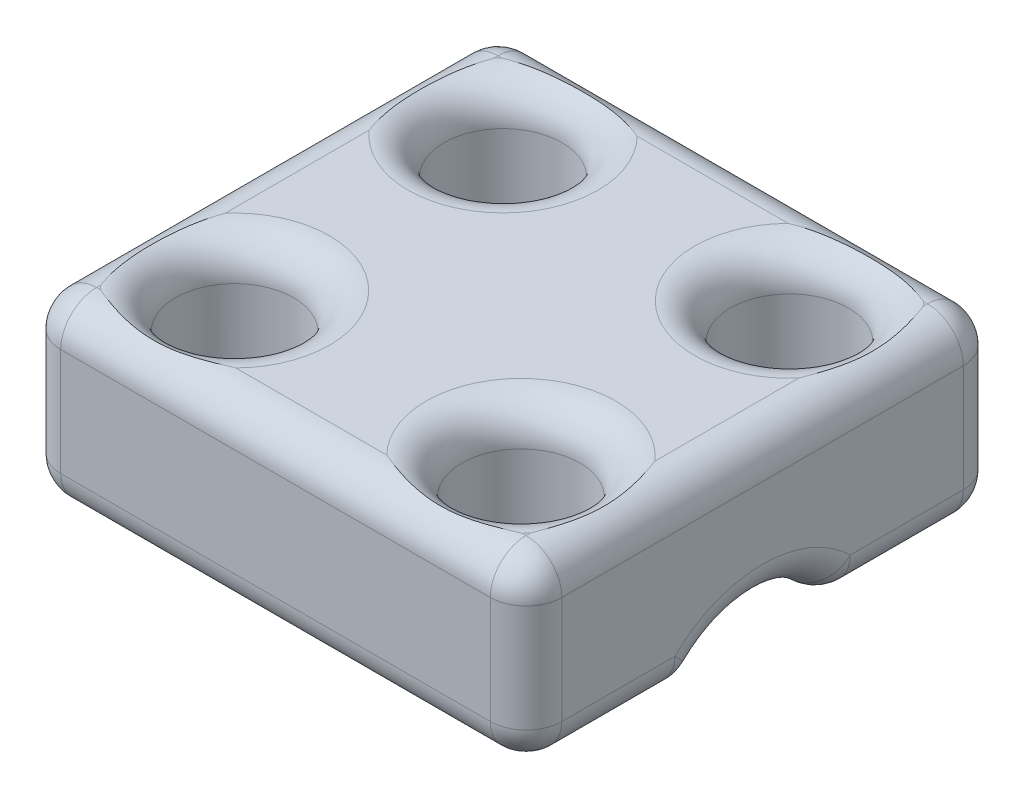
SolidWorks part; units mm, degrees
ref_plane "Front Plane" through (0, 0, 0) normal (0, 0, 1) x (1, 0, 0)
ref_plane "Top Plane" through (0, 0, 0) normal (0, 1, 0) x (1, 0, 0)
ref_plane "Right Plane" through (0, 0, 0) normal (1, 0, 0) x (0, 0, -1)
ref_axis "Axis1" through (0, 5.25, 0) along (0, -1, 0)
sketch "Sketch1" plane through (0, 0, 0) normal (0, 1, 0) x (1, 0, 0)
  line L0 (-47, 6.6067) -> (-11.7936, 6.6067) construction
  line L1 (-49, -6.6067) -> (-35, -6.6067)
  line L2 (-49, -6.6067) -> (-49, 6.6067)
  line L3 (-49, 6.6067) -> (-35, 6.6067)
  line L4 (-35, -6.6067) -> (-35, 6.6067)
  line L5 (-49, -6.6067) -> (-35, 6.6067) construction
  line L6 (-49, 6.6067) -> (-35, -6.6067) construction
  line L7 (-11.7936, -6.6067) -> (-47, -6.6067) construction
  line L8 (-49, 2.5) -> (-49, -2.5) construction
  circle A0 centre (-46, -3.75) radius 1.4 construction
  circle A1 centre (-38, -3.75) radius 1.4 construction
  circle A2 centre (-38, 3.75) radius 1.4 construction
  circle A3 centre (-46, 3.75) radius 1.4 construction
  circle A4 centre (-46, -3.75) radius 1.4 construction
  circle A5 centre (-38, -3.75) radius 1.4 construction
  circle A6 centre (-38, 3.75) radius 1.4 construction
  circle A7 centre (-46, 3.75) radius 1.4 construction
  circle A8 centre (-46, 3.75) radius 1.65
  circle A9 centre (-46, -3.75) radius 1.65
  circle A10 centre (-38, 3.75) radius 1.65
  circle A11 centre (-38, -3.75) radius 1.65
  point P0 (0, 0)
  dimension "D2" = 3.3
  dimension "D1" = 3
extrude "Boss-Extrude1" add sketch "Sketch1" along normal blind 5
sketch "Sketch2" plane through (-49, 0, 0) normal (-1, 0, 0) x (0, 0, 1)
  line L1 (-6.6067, 0) -> (6.6067, 0) construction
  line L4 (0, 0) -> (0, -1.5) construction
  line L5 (-2, 0) -> (2, 0)
  arc A0 (2, 0) -> (-2, 0) centre (0, -1.5) ccw
  dimension "D1" = 2.5
  dimension "D2" = 1.5
extrude "Cut-Extrude1" cut sketch "Sketch2" against normal through all
fillet "Fillet1" radius 1 22 edges at (-42, 0, 2) (-38, 5, 5.4) (-38, 5, -2.1) (-46, 5, -2.1) (-46, 5, 5.4) (-42, 5, 6.6067) (-49, 5, 0) (-42, 5, -6.6067) (-35, 5, 0) (-49, 1, 0) (-49, 2.5, -6.6067) (-49, 0, -4.3034) (-49, 0, 4.3034) (-35, 1, 0) (-42, 0, -2) (-49, 2.5, 6.6067) (-42, 0, 6.6067) (-35, 0, -4.3034) (-35, 0, 4.3034) (-35, 2.5, -6.6067) (-42, 0, -6.6067) (-35, 2.5, 6.6067)
